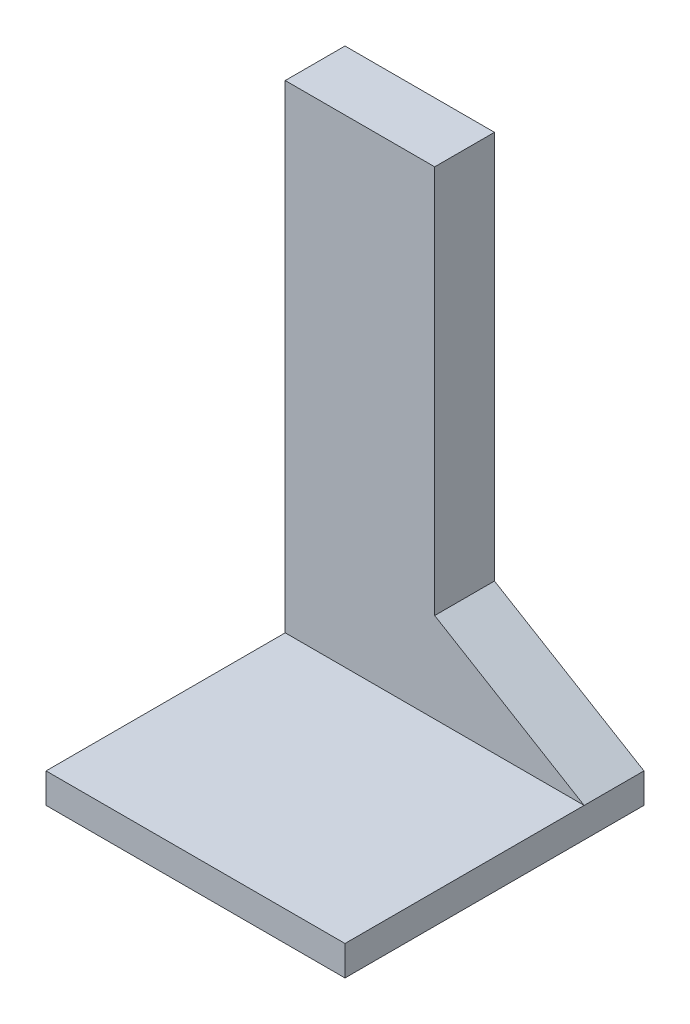
SolidWorks part; units mm, degrees
ref_plane "Front Plane" through (0, 0, 0) normal (0, 0, 1) x (1, 0, 0)
ref_plane "Top Plane" through (0, 0, 0) normal (0, 1, 0) x (1, 0, 0)
ref_plane "Right Plane" through (0, 0, 0) normal (1, 0, 0) x (0, 0, -1)
sketch "Sketch1" plane through (0, 0, 0) normal (0, 1, 0) x (1, 0, 0)
  line L1 (0, 0) -> (-50, 0)
  line L2 (0, 0) -> (0, -50)
  line L3 (0, -50) -> (-50, -50)
  line L4 (-50, 0) -> (-50, -50)
  dimension "D1" = 50
  dimension "D2" = 50
extrude "Boss-Extrude1" add sketch "Sketch1" along normal blind 5
sketch "Sketch2" plane through (0, 0, 0) normal (0, 0, 1) x (1, 0, 0)
  line L0 (0, 5) -> (-25, 20)
  line L1 (-25, 20) -> (-25, 85)
  line L2 (-25, 85) -> (-50, 85)
  line L3 (0, 5) -> (-50, 5)
  line L4 (-50, 5) -> (-50, 85)
  line L5 (0, 5) -> (-50, 5)
  dimension "D1" = 80
  dimension "D2" = 65
  dimension "D3" = 25
extrude "Boss-Extrude2" add sketch "Sketch2" along normal blind 10 contours L2 L4 L3 L0 L1
